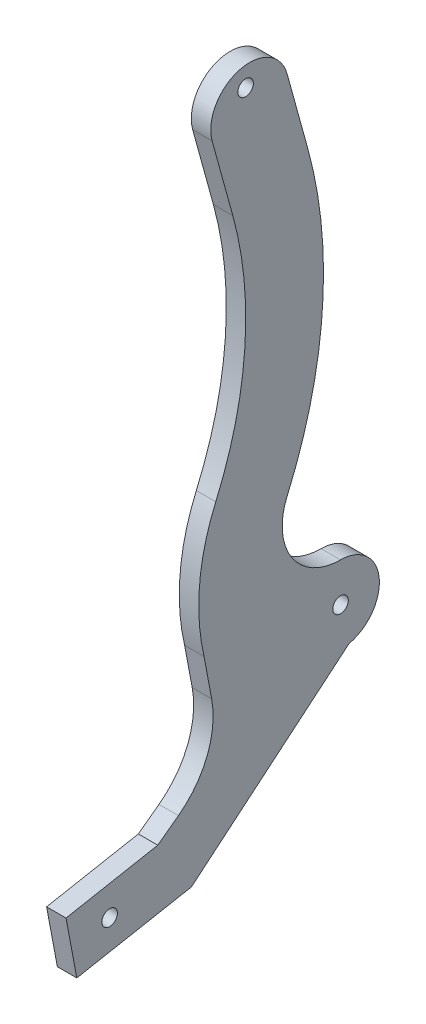
SolidWorks part; units mm, degrees
ref_plane "Front Plane" through (0, 0, 0) normal (0, 0, 1) x (1, 0, 0)
ref_plane "Top Plane" through (0, 0, 0) normal (0, 1, 0) x (1, 0, 0)
ref_plane "Right Plane" through (0, 0, 0) normal (1, 0, 0) x (0, 0, -1)
sketch "Sketch1" plane through (0, 0, 0) normal (1, 0, 0) x (0, 0, -1)
  line L1 (0, 0) -> (-50.8, 0) construction
  line L2 (-50.8, 0) -> (-50.8, 136.525) construction
  line L6 (-44.5699, 7.6328) -> (2.7669, -12.3949)
  line L8 (0, 0) -> (-38.5565, 139.8993) construction
  line L9 (-38.5565, 139.8993) -> (-41.9308, 152.1429)
  line L10 (-38.5565, 139.8993) -> (-35.1821, 127.6558)
  line L12 (0, 12.7) -> (0, 0) construction
  line L14 (-41.9308, 152.1429) -> (-17.4438, 158.8915) construction
  line L15 (-17.4438, 158.8915) -> (-10.6951, 134.4045)
  line L16 (-35.1821, 127.6558) -> (-10.6951, 134.4045) construction
  line L19 (-17.4628, 39.3627) -> (-40.7465, 49.513) construction
  line L20 (-40.7465, 49.513) -> (-32.7787, 67.7904) construction
  circle A0 centre (0, 0) radius 2.54
  arc A1 (2.7669, -12.3949) -> (0, 12.7) centre (0, 0) ccw
  circle A2 centre (-50.8, 136.525) radius 4.7625 construction
  circle A3 centre (-50.8, 136.525) radius 12.7 construction
  arc A11 (-41.9308, 152.1429) -> (-17.4438, 158.8915) centre (-29.6873, 155.5172) cw
  arc A12 (0, 12.7) -> (-17.4628, 39.3627) centre (0, 31.75) cw
  arc A15 (-35.1821, 127.6558) -> (-40.7465, 49.513) centre (-148.413, 96.4492) cw
  arc A16 (-10.6951, 134.4045) -> (-17.4628, 39.3627) centre (-148.413, 96.4492) cw
  arc A17 (-40.7465, 49.513) -> (-44.5699, 7.6328) centre (20.518, 22.8054) ccw
  circle A18 centre (-31.0071, 161.7402) radius 2.54
  dimension "D1" = 5.08
  dimension "D2" = 25.4
  dimension "D3" = 50.8
  dimension "D5" = 9.525
  dimension "D6" = 25.4
  dimension "D8" = 6.35
  dimension "D13" = 12.7
  dimension "D16" = 19.05
  dimension "D12" = 12.7
  dimension "D18" = 25.4
  dimension "D7" = 5.08
  dimension "D4" = 136.525
  dimension "D9" = 6.223
extrude "Boss-Extrude1" add sketch "Sketch1" along normal blind 6.35
sketch "Sketch2" plane through (6.35, 0, 0) normal (1, 0, 0) x (0, 0, -1)
  line L0 (-44.5699, 7.6328) -> (-42.0953, -5.5386)
  line L1 (-52.9447, -33.164) -> (-59.6964, -38.1558)
  line L2 (-59.6964, -38.1558) -> (-89.6524, -43.7837)
  line L3 (-89.6524, -43.7837) -> (-86.1349, -62.5062)
  line L4 (-86.1349, -62.5062) -> (-48.69, -55.4713)
  line L5 (-48.69, -55.4713) -> (2.7669, -12.3949)
  line L6 (-44.5699, 7.6328) -> (2.7669, -12.3949)
  circle A0 centre (-75.412, -50.8) radius 2.54
  arc A2 (-42.0953, -5.5386) -> (-52.9447, -33.164) centre (-69.5549, -10.6975) cw
  dimension "D1" = 9.525
  dimension "D5" = 27.94
  dimension "D8" = 5.08
  dimension "D9" = 67.1073
  dimension "D2" = 19.05
  dimension "D3" = 12.7
  dimension "D4" = 50.8
  dimension "D6" = 30.48
  dimension "D7" = 38.1
  dimension "D10" = 51.4569
extrude "Boss-Extrude2" add sketch "Sketch2" against normal blind 6.35
